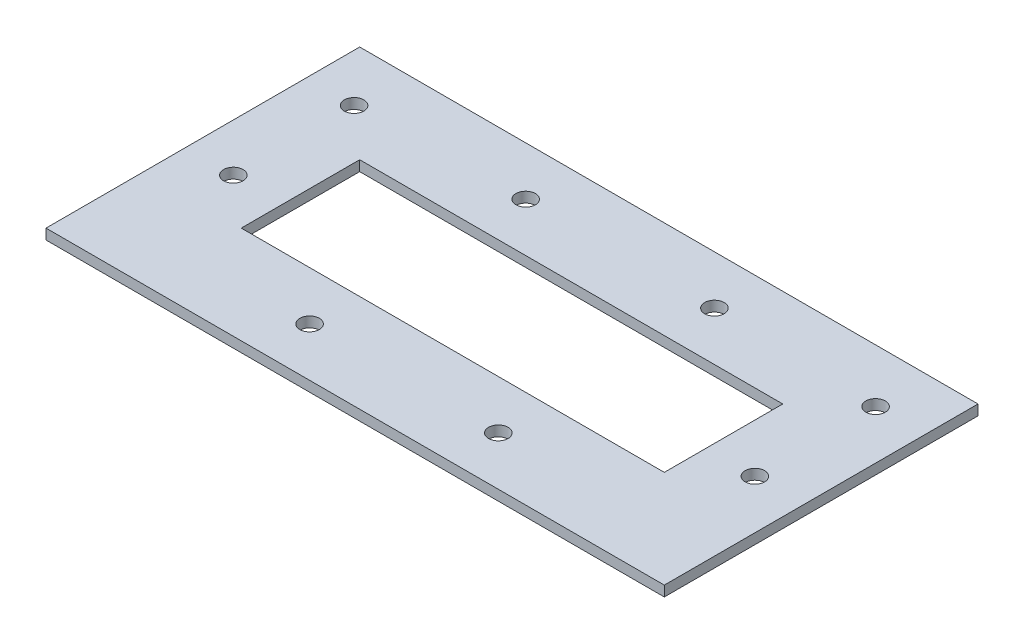
SolidWorks part; units mm, degrees
ref_plane "Front" through (0, 0, 0) normal (0, 0, 1) x (1, 0, 0)
ref_plane "Top" through (0, 0, 0) normal (0, 1, 0) x (1, 0, 0)
ref_plane "Right" through (0, 0, 0) normal (1, 0, 0) x (0, 0, -1)
sketch "Sketch2" plane through (0, 0, 0) normal (0, 1, 0) x (1, 0, 0)
  line L0 (-32.5, 24.0987) -> (-32.5, 9.0987) construction
  line L1 (-47.5, -24.0987) -> (47.5, -24.0987)
  line L2 (-47.5, -24.0987) -> (-47.5, 24.0987)
  line L3 (-47.5, 24.0987) -> (47.5, 24.0987)
  line L4 (47.5, -24.0987) -> (47.5, 24.0987)
  line L5 (-47.5, -24.0987) -> (47.5, 24.0987) construction
  line L6 (-47.5, 24.0987) -> (47.5, -24.0987) construction
  line L7 (-32.5, -9.0987) -> (32.5, -9.0987)
  line L8 (-32.5, -9.0987) -> (-32.5, 9.0987)
  line L9 (-32.5, 9.0987) -> (32.5, 9.0987)
  line L10 (32.5, -9.0987) -> (32.5, 9.0987)
  line L11 (-32.5, -9.0987) -> (32.5, 9.0987) construction
  line L12 (-32.5, 9.0987) -> (32.5, -9.0987) construction
  line L13 (32.5, 9.0987) -> (32.5, 24.0987) construction
  line L14 (-32.5, 16.5987) -> (32.5, 16.5987) construction
  line L15 (32.5, 9.0987) -> (47.5, 9.0987) construction
  line L16 (32.5, -9.0987) -> (47.5, -9.0987) construction
  line L17 (39.9789, 24.0987) -> (39.9789, -24.0987) construction
  line L18 (-47.5, 9.0987) -> (-32.5, 9.0987) construction
  line L19 (-47.5, -9.0987) -> (-32.5, -9.0987) construction
  line L20 (-32.5, -9.0987) -> (-32.5, -24.0987) construction
  line L21 (32.5, -9.0987) -> (32.5, -24.0987) construction
  line L22 (-40.149, 24.0987) -> (-40.149, -24.0987) construction
  line L23 (-32.5, -16.5987) -> (32.5, -16.5987) construction
  circle A0 centre (-14.5, 16.5987) radius 1.5
  circle A1 centre (14.5, 16.5987) radius 1.5
  circle A2 centre (-40.149, 15.8818) radius 1.5
  circle A3 centre (-40.149, -2.6627) radius 1.5
  circle A4 centre (39.9789, 15.8818) radius 1.5
  circle A5 centre (39.9789, -2.6627) radius 1.5
  circle A6 centre (-14.5, -16.5987) radius 1.5
  circle A7 centre (14.5, -16.5987) radius 1.5
  point P0 (0, 0)
  point P6 (0, 0)
  dimension "D7" = 18
  dimension "D8" = 18
  dimension "D1" = 48.1974
  dimension "D2" = 15
  dimension "D3" = 15
  dimension "D4" = 15
  dimension "D5" = 15
  dimension "D6" = 95
extrude "Boss-Extrude2" add sketch "Sketch2" along normal blind 1.5875
